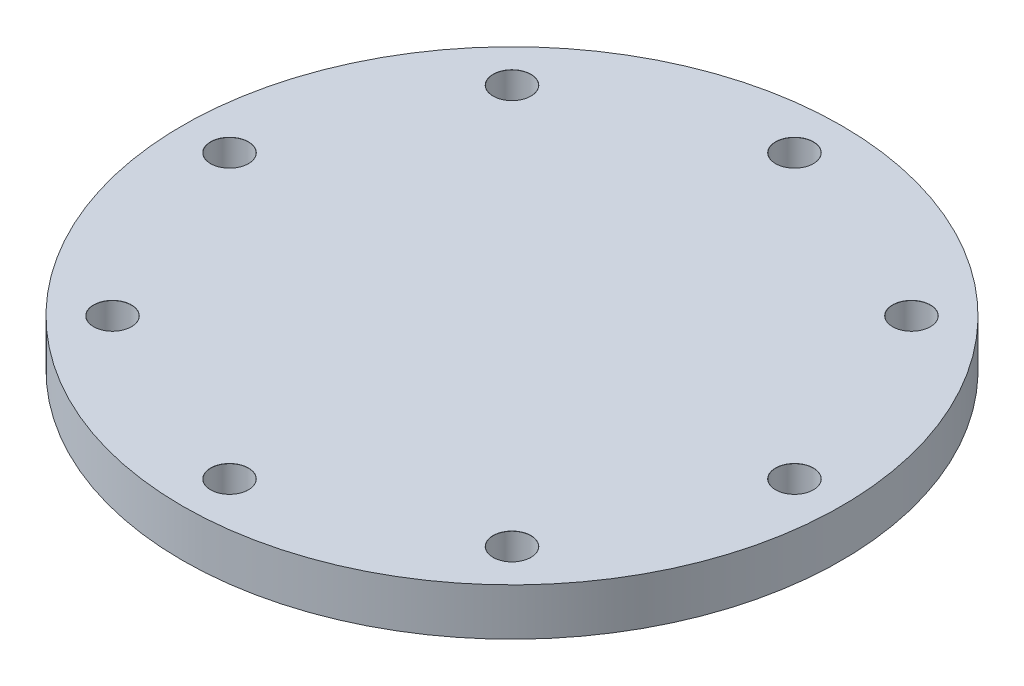
SolidWorks part; units mm, degrees
ref_plane "Front Plane" through (0, 0, 0) normal (0, 0, 1) x (1, 0, 0)
ref_plane "Top Plane" through (0, 0, 0) normal (0, 1, 0) x (1, 0, 0)
ref_plane "Right Plane" through (0, 0, 0) normal (1, 0, 0) x (0, 0, -1)
sketch "草图1" plane through (0, 0, 0) normal (0, 0, 1) x (1, 0, 0)
  line L0 (0, 76.6195) -> (0, -49.9786) construction
  line L13 (0, 0) -> (-70, 0)
  line L14 (0, 0) -> (0, 10)
  line L15 (0, 10) -> (-70, 10)
  line L16 (-70, 0) -> (-70, 10)
  dimension "D1" = 70
  dimension "D2" = 10
revolve "旋转1" add sketch "草图1" angle 360 about L0
sketch "草图8" plane through (0, 10, 0) normal (0, 1, 0) x (1, 0, 0)
  circle A0 centre (0, 0) radius 60
  dimension "D1" = 120
hole_wizard "M8 螺纹孔1" positions "草图9" profile "草图10" tap size "M8" standard "GB" end condition through all
sketch "草图9" plane through (0, 10, 0) normal (0, 1, 0) x (1, 0, 0)
  circle A0 centre (0, 0) radius 60 construction
  point P0 (-60, 0)
cosmetic thread "孔螺蚊线9"
sketch "草图10" plane through (-60, 10, 0) normal (1, 0, 0) x (0, 0, 1)
  line L0 (0, 0) -> (0, 10)
  line L1 (0, 10) -> (4, 10)
  line L2 (4, 10) -> (4, 0.021)
  line L3 (4, 0.021) -> (4.025, 0)
  line L5 (4.025, 0) -> (0, 0)
  line L6 (-4, 0.021) -> (-4.025, 0) construction
  line L11 (0, -6.35) -> (0, 107.95) construction
  dimension "通孔螺纹孔钻头直径" = 8
  dimension "通孔螺纹孔钻头深度" = 10
  dimension "近端锥形沉头孔直径" = 8.05
  dimension "近端锥形沉头孔角度" = 100
pattern_circular "阵列(圆周)2" count 8 over 360 about axis through (0, 76.6195, 0) along (0, -1, 0) of "M8 螺纹孔1"
cosmetic thread "孔螺蚊线10"
cosmetic thread "孔螺蚊线11"
cosmetic thread "孔螺蚊线12"
cosmetic thread "孔螺蚊线13"
cosmetic thread "孔螺蚊线14"
cosmetic thread "孔螺蚊线15"
cosmetic thread "孔螺蚊线16"
ref_axis "基准轴1" through (0, 10, 0) along (0, 1, 0)
